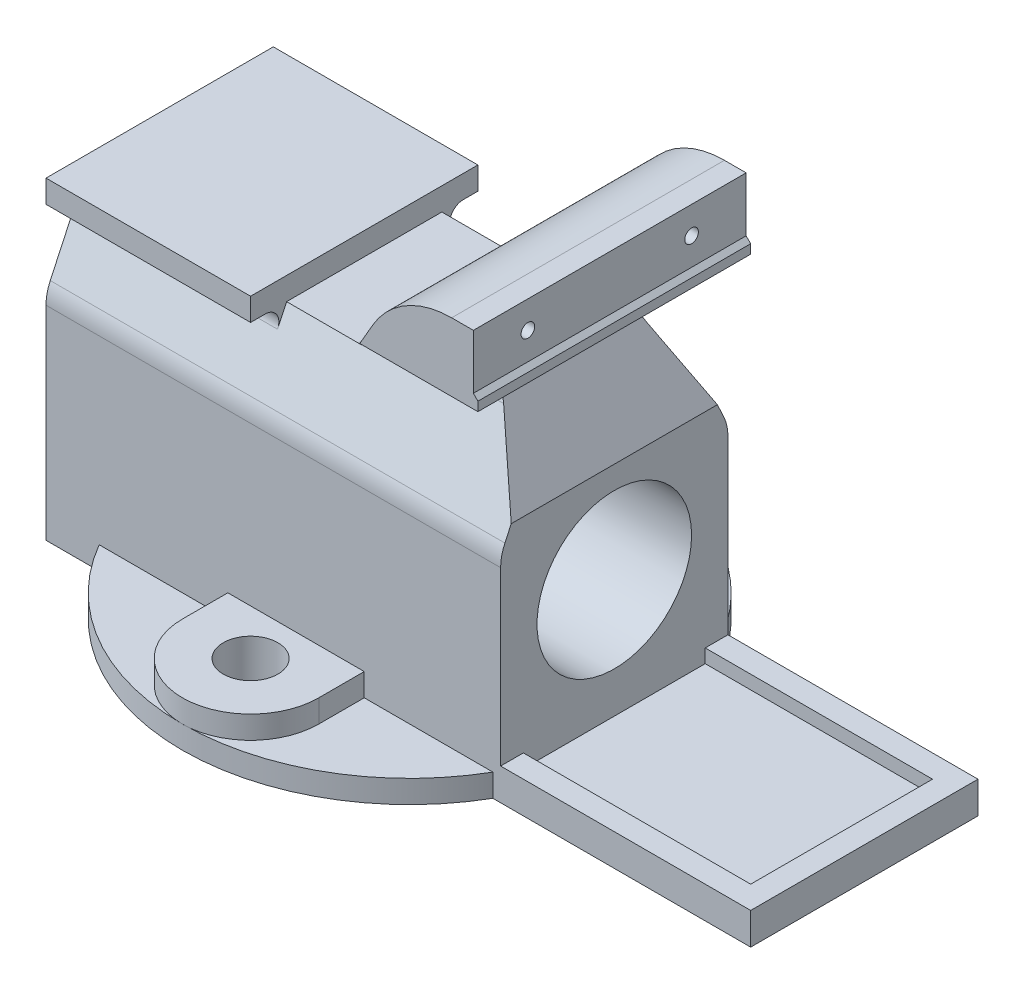
SolidWorks part; units mm, degrees
ref_plane "Front Plane" through (0, 0, 0) normal (0, 0, 1) x (1, 0, 0)
ref_plane "Top Plane" through (0, 0, 0) normal (0, 1, 0) x (1, 0, 0)
ref_plane "Right Plane" through (0, 0, 0) normal (1, 0, 0) x (0, 0, -1)
sketch "Sketch2" plane through (0, 0, 0) normal (0, 0, 1) x (1, 0, 0)
  line L0 (0, 0) -> (0, 27419.7062) construction
  line L1 (0, 0) -> (27419.7062, 0) construction
  line L2 (0, 7) -> (55, 7)
  line L3 (55, 7) -> (55, 0)
  line L4 (55, 0) -> (0, 0)
  line L5 (0, 7) -> (0, 52)
  line L6 (0, 52) -> (-10.1036, 69.5)
  line L7 (-5.7735, 77) -> (0, 77)
  line L8 (0, 77) -> (0, 79)
  line L9 (0, 79) -> (-1, 80)
  line L10 (-1, 80) -> (-1, 92)
  line L11 (0, 0) -> (-100, 0)
  line L12 (-100, 0) -> (-100, 64)
  line L13 (-100, 64) -> (-39.2598, 64)
  line L14 (-30.5996, 69) -> (-23.094, 82)
  line L15 (-5.7735, 92) -> (-1, 92)
  line L16 (-5.7735, 77) -> (-25.9808, 77)
  arc A0 (-10.1036, 69.5) -> (-5.7735, 77) centre (-5.7735, 72) cw
  arc A1 (-39.2598, 64) -> (-30.5996, 69) centre (-39.2598, 74) ccw
  arc A2 (-23.094, 82) -> (-5.7735, 92) centre (-5.7735, 72) cw
  dimension "D4" = 5
  dimension "D12" = 10
  dimension "D1" = 7
  dimension "D2" = 55
  dimension "D3" = 150
  dimension "D5" = 1
  dimension "D6" = 2
  dimension "D7" = 40
  dimension "D8" = 15
  dimension "D9" = 100
  dimension "D10" = 64
  dimension "D11" = 120
  dimension "D13" = 28
  dimension "D14" = 1
extrude "Boss-Extrude1" add sketch "Sketch2" along normal mid plane 50 contours A1 L13 L12 L11 L4 L3 L2 L5 L6 A0 L16 L14 | A2 L14 L16 L7 L8 L9 L10 L15 region at (-44.8695, 31.7298, 0) region at (-11.04, 83.4885, 0)
sketch "Sketch3" plane through (0, 7, 0) normal (0, 1, 0) x (1, 0, 0)
  line L0 (0, 20) -> (50, 20)
  line L1 (0, -25) -> (0, 25) construction
  line L2 (50, 20) -> (50, -20)
  line L3 (50, -20) -> (0, -20)
  line L5 (55, -25) -> (55, 25) construction
  line L7 (0, 20) -> (0, -20)
  line L8 (0, 25) -> (55, 25) construction
  line L9 (0, -25) -> (55, -25) construction
  dimension "D1" = 5
  dimension "D2" = 5
  dimension "D3" = 5
extrude "Cut-Extrude1" cut sketch "Sketch3" against normal blind 3
extrude "Boss-Extrude5" add sketch "Sketch2<4>" along normal mid plane 60 contours A2 L14 L16 L7 L8 L9 L10 L15 region at (-11.04, 83.4885, 0)
sketch "Sketch2<4>" plane through (0, 0, 0) normal (0, 0, 1) x (1, 0, 0) same geometry as "Sketch2"
sketch "Sketch4" plane through (-1, 0, 0) normal (1, 0, 0) x (0, 0, -1)
  line L0 (0, 0) -> (0, 145.2084) construction
  line L1 (-30, 92) -> (30, 92) construction
  circle A0 centre (-18, 86) radius 1.5
  circle A1 centre (18, 86) radius 1.5
  dimension "D1" = 36
  dimension "D2" = 3
  dimension "D3" = 6
extrude "Cut-Extrude2" cut sketch "Sketch4" against normal blind 5
sketch "Sketch5" plane through (0, 0, 0) normal (1, 0, 0) x (0, 0, -1)
  line L0 (-25, 0) -> (25, 0) construction
  circle A0 centre (0, 30) radius 17
  dimension "D1" = 30
  dimension "D2" = 34
extrude "Cut-Extrude3" cut sketch "Sketch5" against normal through all
sketch "Sketch6" plane through (-100, 0, 0) normal (-1, 0, 0) x (0, 0, 1)
  circle A0 centre (0, 52.5) radius 2.5
  circle A1 centre (0, 7.5) radius 2.5
  circle A2 centre (0, 30) radius 22.5 construction
  point P9 (0, 0)
  dimension "D1" = 5
  dimension "D2" = 45
extrude "Cut-Extrude4" cut sketch "Sketch6" against normal blind 10
sketch "Sketch8" plane through (0, 0, 0) normal (0, -1, 0) x (1, 0, 0)
  line L0 (-100, 25) -> (-100, -25) construction
  line L1 (-88.3013, 25) -> (-1.6987, 25)
  line L3 (-88.3013, -25) -> (-1.6987, -25)
  line L5 (-60, 25) -> (-60, 35)
  line L6 (-30, 35) -> (-30, 25)
  line L7 (-30, 25) -> (-60, 25)
  line L8 (0, 0) -> (-35.9078, 0) construction
  line L9 (-60, -25) -> (-60, -35)
  line L10 (-30, -35) -> (-30, -25)
  line L11 (55, 25) -> (-100, 25) construction
  line L12 (55, -25) -> (-100, -25) construction
  circle A0 centre (-45, 0) radius 50
  arc A1 (-60, 35) -> (-30, 35) centre (-45, 35) cw
  circle A2 centre (-45, 35) radius 6
  arc A3 (-60, -35) -> (-30, -35) centre (-45, -35) ccw
  circle A4 centre (-45, -35) radius 6
  dimension "D1" = 100
  dimension "D2" = 5
  dimension "D3" = 15
  dimension "D4" = 12
extrude "Boss-Extrude2" add sketch "Sketch8" against normal blind 5 contours A3 L9 A0 | A3 A0 L10 | L9 A3 L10 L3 A4 | A0 A1 L6 | L5 A1 A0 L1 | A1 L5 L1 L6 A2 region at (-69.4227, 0, 34.5867) region at (-59.6095, 0, 30) region at (-69.4227, 0, -34.5867) region at (-20.5773, 0, 34.5867) region at (-45, 0, -25.3905) region at (-20.5773, 0, -34.5867)
extrude "Boss-Extrude3" add sketch "Sketch8<3>" against normal blind 10 contours L9 A3 L10 L3 A4 | A1 L5 L1 L6 A2 region at (-59.6095, 0, 30) region at (-45, 0, -25.3905)
sketch "Sketch8<3>" plane through (0, 0, 0) normal (0, -1, 0) x (1, 0, 0) same geometry as "Sketch8"
sketch "Sketch12" plane through (0, 0, 0) normal (1, 0, 0) x (0, 0, -1)
  line L0 (0, 0) -> (0, 71.5313) construction
  line L1 (-25, 0) -> (25, 0) construction
  line L2 (25, 47) -> (15.6544, 67.0417)
  line L3 (25, 7) -> (25, 52) construction
  line L4 (-30, 77) -> (30, 77) construction
  line L5 (21.9986, 77) -> (25, 77)
  line L6 (25, 77) -> (25, 47)
  line L8 (-25, 77) -> (-25, 47)
  line L9 (-21.9986, 77) -> (-25, 77)
  line L10 (-25, 47) -> (-15.6544, 67.0417)
  arc A0 (15.6544, 67.0417) -> (21.9986, 77) centre (21.9986, 70) cw
  arc A1 (-15.6544, 67.0417) -> (-21.9986, 77) centre (-21.9986, 70) ccw
  point P14 (11.0108, 77)
  dimension "D1" = 7
  dimension "D2" = 30
  dimension "D3" = 25
extrude "Cut-Extrude5" cut sketch "Sketch12" against normal through all
sketch "Sketch10" plane through (0, 64, 0) normal (0, 1, 0) x (1, 0, 0)
  line L1 (-100, 25) -> (-55, 25)
  line L2 (-100, 25) -> (-100, -25)
  line L3 (-100, -25) -> (-55, -25)
  line L4 (-55, 25) -> (-55, -25)
  line L5 (-100, 25) -> (-39.2598, 25) construction
  line L6 (-100, -25) -> (-39.2598, -25) construction
  line L7 (-100, -17.0728) -> (-100, 17.0728) construction
  dimension "D1" = 45
extrude "Boss-Extrude4" add sketch "Sketch10" along normal blind 5
fillet "Fillet1" radius 3 2 edges at (-77.5, 64, -17.0728) (-77.5, 64, 17.0728)
fillet "Fillet2" radius 10 2 edges at (-50, 47, -25) (-50, 47, 25)
sketch "Sketch13" plane through (0, 0, 0) normal (0, -1, 0) x (1, 0, 0)
  circle A0 centre (-45, 0) radius 35 construction
  point P2 (-45, 35)
  point P3 (-45, -35)
  point P5 (0, 0)
  dimension "D1" = 70
